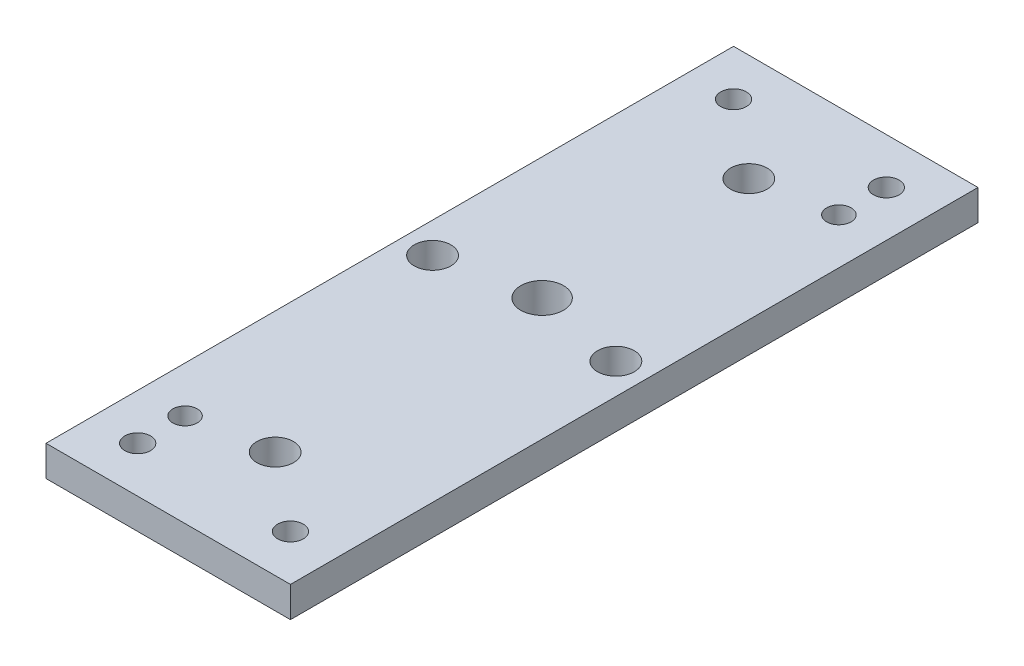
SolidWorks part; units mm, degrees
material "K110"
ref_plane "Front Plane" through (0, 0, 0) normal (0, 0, 1) x (1, 0, 0)
ref_plane "Top Plane" through (0, 0, 0) normal (0, 1, 0) x (1, 0, 0)
ref_plane "Right Plane" through (0, 0, 0) normal (1, 0, 0) x (0, 0, -1)
sketch "Sketch1" plane through (0, 0, 0) normal (0, 1, 0) x (1, 0, 0)
  line L1 (-40, -112.5) -> (40, -112.5)
  line L2 (-40, -112.5) -> (-40, 112.5)
  line L3 (-40, 112.5) -> (40, 112.5)
  line L4 (40, -112.5) -> (40, 112.5)
  line L5 (-40, -112.5) -> (40, 112.5) construction
  line L6 (-40, 112.5) -> (40, -112.5) construction
  point P0 (0, 0)
  dimension "D1" = 225
  dimension "D2" = 80
extrude "Boss-Extrude1" add sketch "Sketch1" against normal blind 10
sketch "Sketch2" plane through (0, 0, 0) normal (0, 1, 0) x (1, 0, 0)
  circle A0 centre (0, 77.5) radius 6 construction
  circle A1 centre (30, 4) radius 6 construction
  circle A2 centre (-30, 4) radius 6 construction
  circle A3 centre (0, -77.5) radius 6 construction
  circle A4 centre (0, 77.5) radius 6
  circle A5 centre (30, 4) radius 6
  circle A6 centre (-30, 4) radius 6
  circle A7 centre (0, -77.5) radius 6
extrude "Cut-Extrude1" cut sketch "Sketch2" against normal up to next
hole_wizard "M8 Clearance Hole1" positions "Sketch6" profile "Sketch5" hole size "M8" standard "ISO" end condition through all
sketch "Sketch6" plane through (0, 0, 0) normal (0, 1, 0) x (1, 0, 0)
  point P0 (-25, 97.5)
  point P3 (25, 97.5)
  point P6 (25, -97.5)
  point P9 (-25, -97.5)
sketch "Sketch5" plane through (-25, 0, -97.5) normal (1, 0, 0) x (0, 0, 1)
  line L0 (0, 0) -> (0, 10)
  line L1 (0, 10) -> (4.2, 10)
  line L2 (4.2, 10) -> (4.2, 0)
  line L5 (4.2, 0) -> (0, 0)
  line L11 (0, -6.35) -> (0, 107.95) construction
  dimension "Thru Hole Dia." = 8.4
  dimension "Thru Hole Depth" = 10
hole_wizard "Ø8.0mm Dowel Hole1" positions "Sketch9" profile "Sketch8" hole size "Ø8.0" standard "ISO" end condition through all
sketch "Sketch9" plane through (0, 0, 0) normal (0, 1, 0) x (1, 0, 0)
  point P0 (25, 81.975)
  point P3 (-25, -82)
sketch "Sketch8" plane through (25, 0, -81.975) normal (1, 0, 0) x (0, 0, 1)
  line L0 (0, 0) -> (0, 10)
  line L1 (0, 10) -> (4, 10)
  line L2 (4, 10) -> (4, 0)
  line L5 (4, 0) -> (0, 0)
  line L11 (0, -6.35) -> (0, 107.95) construction
  dimension "Thru Hole Dia." = 8
  dimension "Thru Hole Depth" = 10
sketch "Sketch10" plane through (0, 0, 0) normal (0, 1, 0) x (1, 0, 0)
  circle A0 centre (0, 9.86) radius 7 construction
  circle A1 centre (0, 9.86) radius 7
extrude "Cut-Extrude3" cut sketch "Sketch10" against normal up to next
